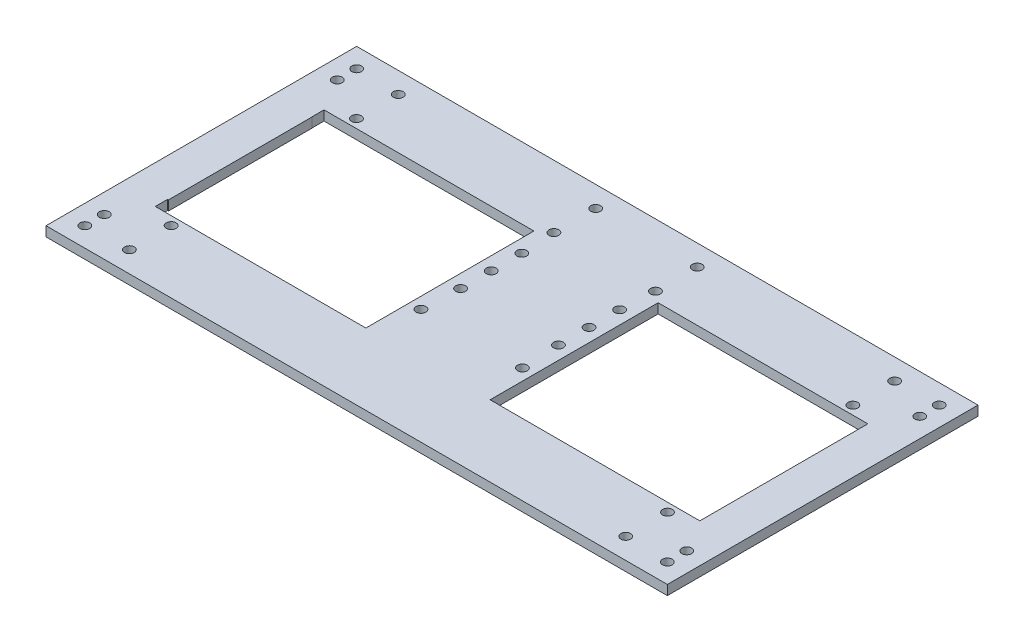
SolidWorks part; units mm, degrees
ref_plane "Front" through (0, 0, 0) normal (0, 0, 1) x (1, 0, 0)
ref_plane "Top" through (0, 0, 0) normal (0, 1, 0) x (1, 0, 0)
ref_plane "Right" through (0, 0, 0) normal (1, 0, 0) x (0, 0, -1)
sketch "Sketch1" plane through (0, 0, 0) normal (0, 1, 0) x (1, 0, 0)
  line L0 (0, -50.8) -> (203.2, -50.8)
  line L1 (0, 0) -> (203.2, 0)
  line L2 (0, 0) -> (0, -101.6)
  line L3 (0, -101.6) -> (203.2, -101.6)
  line L4 (203.2, 0) -> (203.2, -101.6)
  line L5 (101.6, 0) -> (0, 0)
  line L6 (50.8, 0) -> (50.8, -101.6)
  line L7 (101.6, 0) -> (203.2, 0)
  line L8 (152.4, 0) -> (152.4, -101.6)
  line L9 (12.7, -27.3231) -> (12.7, -74.2769)
  line L10 (81.28, -27.3231) -> (81.28, -74.2769)
  line L11 (12.7, -27.3231) -> (81.28, -27.3231)
  line L12 (12.7, -74.2769) -> (81.28, -74.2769)
  line L14 (121.92, -27.3231) -> (121.92, -74.2769)
  line L15 (101.6, 0) -> (101.6, -101.6)
  line L16 (12.7, 0) -> (12.7, -13.6616)
  line L17 (12.7, -13.6616) -> (12.7, -27.3231)
  line L18 (12.7, -74.2769) -> (12.7, -87.9384)
  line L19 (12.7, -87.9384) -> (12.7, -101.6)
  line L20 (190.5, -27.3231) -> (121.92, -27.3231)
  line L22 (190.5, -74.2769) -> (121.92, -74.2769)
  line L23 (190.5, -27.3231) -> (121.92, -27.3231)
  line L31 (121.92, -27.3231) -> (121.92, -23.3231)
  line L32 (190.5, -23.3231) -> (121.92, -23.3231)
  line L33 (190.5, -74.2769) -> (121.92, -74.2769)
  line L34 (190.5, -74.2769) -> (190.5, -78.2769)
  line L35 (121.92, -74.2769) -> (121.92, -78.2769)
  line L36 (190.5, -78.2769) -> (121.92, -78.2769)
  line L37 (81.28, -74.2769) -> (81.28, -78.2769)
  line L38 (81.28, -74.2769) -> (12.4051, -74.2769)
  line L39 (81.28, -78.2769) -> (12.4051, -78.2769)
  line L40 (12.4051, -74.2769) -> (12.4051, -78.2769)
  line L41 (81.28, -27.3231) -> (81.28, -23.3231)
  line L42 (81.28, -27.3231) -> (12.6484, -27.3231)
  line L43 (81.28, -23.3231) -> (12.6484, -23.3231)
  line L44 (12.6484, -27.3231) -> (12.6484, -23.3231)
  line L45 (118.2, -6.8308) -> (118.2, -20.4924)
  line L46 (190.5, -23.3231) -> (190.5, -27.3231)
  line L47 (190.5, -74.2769) -> (190.5, -27.3231)
  line L48 (117.6, -51.6) -> (85.6, -51.6)
  line L49 (117.6, -51.6) -> (117.6, -41.6)
  line L50 (117.6, -41.6) -> (117.6, -31.6)
  line L51 (117.6, -41.6) -> (85.6, -41.6)
  line L52 (117.6, -31.6) -> (85.6, -31.6)
  circle A0 centre (12.7, -6.8308) radius 1.6
  circle A1 centre (12.7, -81.1076) radius 1.6
  circle A2 centre (12.7, -94.7692) radius 1.6
  circle A3 centre (12.7, -20.4924) radius 1.6
  circle A4 centre (190.5, -94.7692) radius 1.6
  circle A5 centre (190.5, -81.1076) radius 1.6
  circle A6 centre (190.5, -6.8308) radius 1.6
  circle A7 centre (190.5, -20.4924) radius 1.6
  circle A8 centre (118.2, -6.8308) radius 1.6
  circle A15 centre (85, -6.8308) radius 1.6
  circle A20 centre (118.2, -20.4924) radius 1.6
  circle A23 centre (85, -20.4924) radius 1.6
  circle A24 centre (182.769, -6.8308) radius 1.6
  circle A25 centre (182.769, -20.4924) radius 1.6
  circle A26 centre (182.769, -94.7692) radius 1.6
  circle A27 centre (182.769, -81.1076) radius 1.6
  circle A28 centre (20.431, -94.7692) radius 1.6
  circle A29 centre (20.431, -81.1076) radius 1.6
  circle A30 centre (20.431, -20.4924) radius 1.6
  circle A31 centre (20.431, -6.8308) radius 1.6
  circle A32 centre (85, -63.9814) radius 1.6
  circle A33 centre (118.2, -63.9814) radius 1.6
  circle A34 centre (117.6, -51.6) radius 1.6
  circle A35 centre (85.6, -51.6) radius 1.6
  circle A36 centre (117.6, -41.6) radius 1.6
  circle A37 centre (117.6, -31.6) radius 1.6
  circle A38 centre (85.6, -31.6) radius 1.6
  circle A39 centre (85.6, -41.6) radius 1.6
  point P15 (12.7, -50.8)
  point P16 (12.7, -50.8)
  point P19 (81.28, -50.8)
  point P60 (101.6, -50.8)
  point P66 (101.6, -51.6)
  dimension "D5" = 32
  dimension "D7" = 46.9537
  dimension "D11" = 43.489
  dimension "D13" = 10
  dimension "D1" = 101.6
  dimension "D2" = 203.2
  dimension "D3" = 30.48
  dimension "D4" = 38.1
  dimension "D6" = 0
  dimension "D8" = 4
  dimension "D9" = 4
  dimension "D10" = 85
  dimension "D12" = 13.6616
  dimension "D14" = 10
  dimension "D15" = 50
  dimension "D16" = 0
extrude "Boss-Extrude1" add sketch "Sketch1" against normal blind 3.175 contours L47 L0 L4 L7 L8 L32 L46 A25 A24 A6 A7 | L47 L34 L36 L8 L3 L4 L0 A26 A4 A5 A27 | A37 L50 L0 L14 L31 L32 L8 L1 L15 L52 A20 A8 | A36 L49 A34 L48 L15 L3 L8 L36 L35 L14 L0 L50 A33 | A39 L0 L10 L37 L39 L6 L3 L15 A35 A32 | A38 L15 L5 L6 L43 L41 L10 L0 A15 A23 | A3 L17 L43 L6 L5 L16 A0 A30 A31 | A3 L17 L16 A0 L1 L2 L0 L9 L42 L44 L43 | A2 L19 L18 A1 L39 L40 L38 L9 L0 L2 L3 | A2 L19 L3 L6 L39 L18 A1 A29 A28 | A37 L52 L0 L50 | A36 L51 L15 L0 L49 | A34 L49 L0 L15 L48 | A35 L48 L15 L0 | A6 | A7 | A5 | A4 | A2 | A1 | A3 | A0 region at (6.2763, 0, 25.5482) region at (6.2668, 0, 76.0514) region at (32.1315, 0, 11.6058) region at (32.1315, 0, 89.9942) region at (80.9978, 0, 19.6686) region at (80.9564, 0, 82.2054) region at (124.9243, 0, 15.072) region at (122.2436, 0, 82.2054) region at (94.3652, 0, 51.199) region at (182.0377, 0, 17.5214) region at (109.4113, 0, 36.6) region at (182.0377, 0, 84.0786) region at (108.8348, 0, 51.199) region at (109.4575, 0, 46.2313)
sketch "Sketch2" plane through (0, -3.175, 0) normal (0, -1, 0) x (1, 0, 0)
  line L0 (101.6, 0) -> (101.6, 101.6)
  line L1 (0, 0) -> (203.2, 0) construction
  line L2 (0, 101.6) -> (203.2, 101.6) construction
  line L3 (196.85, 50.8) -> (6.35, 50.8)
  line L4 (6.35, 12.7) -> (6.35, 88.9)
  line L5 (196.85, 12.7) -> (196.85, 88.9)
  line L6 (196.85, 12.7) -> (196.85, 6.35)
  line L7 (6.35, 88.9) -> (6.35, 95.25)
  circle A0 centre (196.85, 12.7) radius 1.6
  circle A1 centre (196.85, 88.9) radius 1.6
  circle A2 centre (6.35, 88.9) radius 1.6
  circle A3 centre (6.35, 12.7) radius 1.6
  circle A4 centre (196.85, 6.35) radius 1.6
  circle A5 centre (6.35, 6.35) radius 1.6
  circle A6 centre (6.35, 95.25) radius 1.6
  circle A7 centre (196.85, 95.25) radius 1.6
  point P9 (101.6, 50.8)
  point P12 (6.35, 50.8)
  point P15 (196.85, 50.8)
  dimension "D1" = 190.5
  dimension "D5" = 6.35
  dimension "D2" = 76.2
  dimension "D3" = 76.2
  dimension "D4" = 6.35
extrude "Cut-Extrude1" cut sketch "Sketch2" against normal blind 10 contours A1 | L7 A2 L4 | L4 A2 L7 | A6 | A5 | A3 | A4 | A0 | A7 region at (7.4494, -3.175, 13.7994) region at (5.2506, -3.175, 96.3494) region at (5.6709, -3.175, 88.9) region at (7.0291, -3.175, 88.9) region at (195.7506, -3.175, 89.9994) region at (6.35, -3.175, 6.35)
